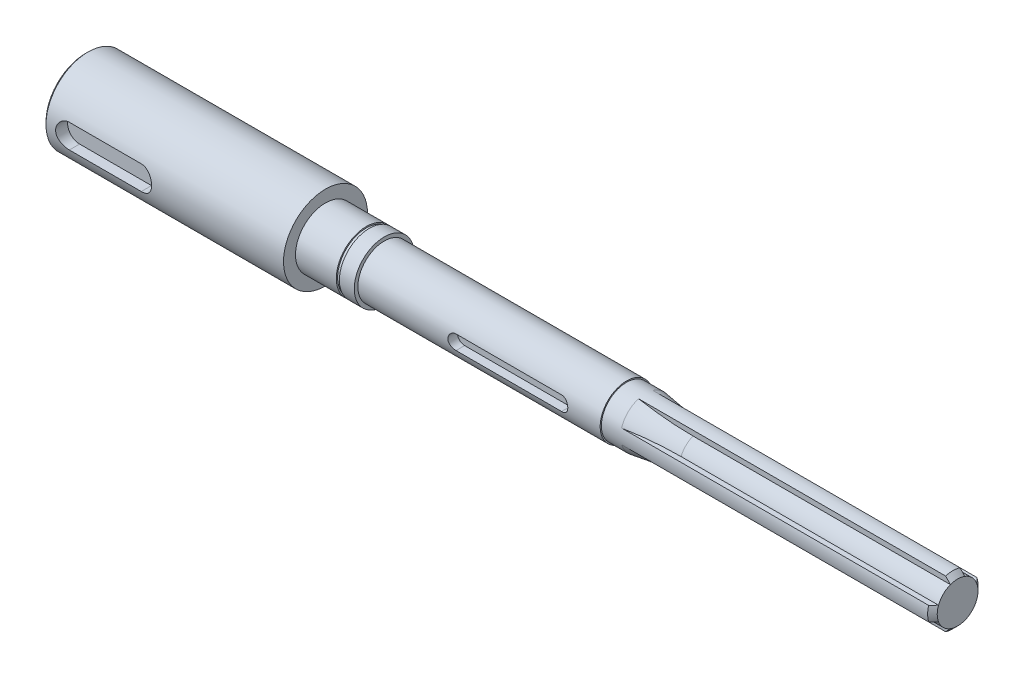
SolidWorks part; units mm, degrees
ref_plane "前视基准面" through (0, 0, 0) normal (0, 0, 1) x (1, 0, 0)
ref_plane "上视基准面" through (0, 0, 0) normal (0, 1, 0) x (1, 0, 0)
ref_plane "右视基准面" through (0, 0, 0) normal (1, 0, 0) x (0, 0, -1)
sketch "草图1" plane through (0, 0, 0) normal (0, 0, 1) x (1, 0, 0)
  line L0 (0, 0) -> (0, 17.5)
  line L1 (0, -19.25) -> (0, 19.25) construction
  line L2 (0, 17.5) -> (100, 17.5)
  line L3 (100, 17.5) -> (100, 12.5)
  line L4 (100, 12.5) -> (124.5, 12.5)
  line L5 (124.5, 12.5) -> (124.5, 11)
  line L6 (124.5, 11) -> (225.5, 11)
  line L7 (225.5, 11) -> (225.5, 10.5)
  line L8 (225.5, 10.5) -> (363.5, 10.5)
  line L9 (363.5, 10.5) -> (363.5, 0)
  line L10 (363.5, 0) -> (0, 0) construction
  line L11 (0, 0) -> (363.5, 0)
  dimension "D1" = 21
  dimension "D2" = 22
  dimension "D3" = 25
  dimension "D4" = 35
  dimension "D5" = 100
  dimension "D6" = 24.5
  dimension "D7" = 138
  dimension "D8" = 363.5
revolve "旋转1" add sketch "草图1" angle 360 about L10
chamfer "倒角1" distance 1 angle 45 1 edges at (0, 17.5, 0)
chamfer "倒角2" distance 2 angle 45 1 edges at (363.5, 10.5, 0)
sketch "草图2" plane through (100, 0, 0) normal (1, 0, 0) x (0, 0, -1)
  circle A0 centre (0, 0) radius 11.95
  dimension "D1" = 23.9
extrude "切除-拉伸1" cut sketch "草图2" along normal blind 1.3 from offset 17 flip side to cut
sketch "草图3" plane through (363.5, 0, 0) normal (1, 0, 0) x (0, 0, -1)
  line L0 (0, 0) -> (2.2857, 7.6665) construction
  line L1 (-3, -10.0623) -> (3, -10.0623) construction
  line L2 (-3, -10.0623) -> (-3, -7.4162)
  line L3 (-3, 10.0623) -> (3, 10.0623) construction
  line L4 (3, -7.4162) -> (3, 7.4162) construction
  line L5 (-2.2857, -7.6665) -> (0, 0) construction
  line L6 (-3, 10.0623) -> (-2.2857, 7.6665) construction
  line L7 (2.2857, 7.6665) -> (3, 10.0623) construction
  line L8 (-2.2857, 7.6665) -> (0, 0) construction
  line L9 (0, 0) -> (2.2857, -7.6665) construction
  line L10 (-3, -7.4162) -> (-3, 7.4162) construction
  line L11 (-3, 7.4162) -> (-3, 10.0623)
  line L12 (3, 7.4162) -> (3, 10.0623)
  line L13 (3, -10.0623) -> (3, -7.4162)
  line L14 (2.2857, -7.6665) -> (3, -10.0623) construction
  line L15 (-3, -10.0623) -> (-2.2857, -7.6665) construction
  line L16 (7.4162, 3) -> (10.0623, 3)
  line L17 (7.4162, -3) -> (10.0623, -3)
  line L18 (3, -7.4162) -> (3, -10.0623)
  line L19 (-3, -7.4162) -> (-3, -10.0623)
  line L20 (-7.4162, -3) -> (-10.0623, -3)
  line L21 (-7.4162, 3) -> (-10.0623, 3)
  arc A0 (-3, 7.4162) -> (-7.4162, 3) centre (0, 0) ccw
  circle A1 centre (0, 0) radius 10.5 construction
  circle A2 centre (0, 0) radius 10.5 construction
  arc A3 (-3, -10.0623) -> (3, -10.0623) centre (0, 0) ccw construction
  arc A4 (3, 7.4162) -> (2.2857, 7.6665) centre (0, 0) ccw construction
  arc A5 (2.2857, 7.6665) -> (-2.2857, 7.6665) centre (0, 0) ccw construction
  arc A6 (-2.2857, 7.6665) -> (-3, 7.4162) centre (0, 0) ccw construction
  arc A7 (-2.2857, -7.6665) -> (2.2857, -7.6665) centre (0, 0) ccw construction
  arc A8 (3, -7.4162) -> (7.4162, -3) centre (0, 0) ccw
  arc A9 (-3, -7.4162) -> (-2.2857, -7.6665) centre (0, 0) ccw construction
  arc A10 (2.2857, -7.6665) -> (3, -7.4162) centre (0, 0) ccw construction
  arc A11 (-3, 10.0623) -> (-10.0623, 3) centre (0, 0) ccw
  arc A12 (3, -10.0623) -> (10.0623, -3) centre (0, 0) ccw
  arc A13 (3, 10.0623) -> (-3, 10.0623) centre (0, 0) ccw construction
  arc A14 (10.0623, -3) -> (10.0623, 3) centre (0, 0) ccw construction
  arc A15 (-3, -10.0623) -> (3, -10.0623) centre (0, 0) ccw construction
  arc A16 (-10.0623, 3) -> (-10.0623, -3) centre (0, 0) ccw construction
  arc A17 (-7.4162, 3) -> (-7.4162, -3) centre (0, 0) ccw construction
  arc A18 (-7.4162, -3) -> (-3, -7.4162) centre (0, 0) ccw
  arc A19 (7.4162, -3) -> (7.4162, 3) centre (0, 0) ccw construction
  arc A20 (7.4162, 3) -> (3, 7.4162) centre (0, 0) ccw
  arc A21 (-10.0623, 3) -> (-10.0623, -3) centre (0, 0) ccw construction
  arc A22 (-10.0623, -3) -> (-3, -10.0623) centre (0, 0) ccw
  arc A23 (10.0623, -3) -> (10.0623, 3) centre (0, 0) ccw construction
  arc A24 (10.0623, 3) -> (3, 10.0623) centre (0, 0) ccw
  circle M5 centre (0, 0) radius 8.5
  dimension "D1" = 16
  dimension "D2" = 6
  dimension "D3" = 4
extrude "切除-拉伸2" cut sketch "草图3" against normal blind 130 contours L11 A11 L21 M5 | L16 A24 L12 M5 | L13 A12 L17 M5 | L20 A22 L2 M5 | L21 A16 L20 A18 L2 A3 L13 A8 L17 A14 L16 A20 L12 A13 L11 A0 region at (363.5, -6.5175, 6.5175) region at (363.5, -6.5175, -6.5175) region at (363.5, 6.5175, 6.5175) region at (363.5, 6.5175, -6.5175)
fillet "圆角1" radius 130 4 edges at (233.5, 6.0104, 6.0104) (233.5, -6.0104, 6.0104) (233.5, -6.0104, -6.0104) (233.5, 6.0104, -6.0104)
sketch "草图4" plane through (0, 0, 0) normal (0, 0, 1) x (1, 0, 0)
  line L0 (165, 0) -> (209, 0) construction
  line L1 (19.25, 0) -> (-19.25, 0) construction
  line L2 (165, 3) -> (209, 3)
  line L3 (165, -3) -> (209, -3)
  line L4 (124.5, -11) -> (124.5, 11) construction
  arc A0 (165, 3) -> (165, -3) centre (165, 0) ccw
  arc A1 (209, -3) -> (209, 3) centre (209, 0) ccw
  point P5 (187, 0)
  dimension "D1" = 50
  dimension "D2" = 37.5
  dimension "D3" = 6
extrude "切除-拉伸3" cut sketch "草图4" along normal through all from offset 7
sketch "草图5" plane through (0, 0, 0) normal (0, 0, 1) x (1, 0, 0)
  line L0 (10, 0) -> (40, 0) construction
  line L1 (19.25, 0) -> (-19.25, 0) construction
  line L2 (10, 5) -> (40, 5)
  line L3 (10, -5) -> (40, -5)
  line L4 (0, -19.25) -> (0, 19.25) construction
  arc A0 (10, 5) -> (10, -5) centre (10, 0) ccw
  arc A1 (40, -5) -> (40, 5) centre (40, 0) ccw
  point P5 (25, 0)
  point P12 (5, 0)
  dimension "D1" = 40
  dimension "D2" = 5
  dimension "D3" = 10
extrude "切除-拉伸4" cut sketch "草图5" along normal through all from offset 12.5
